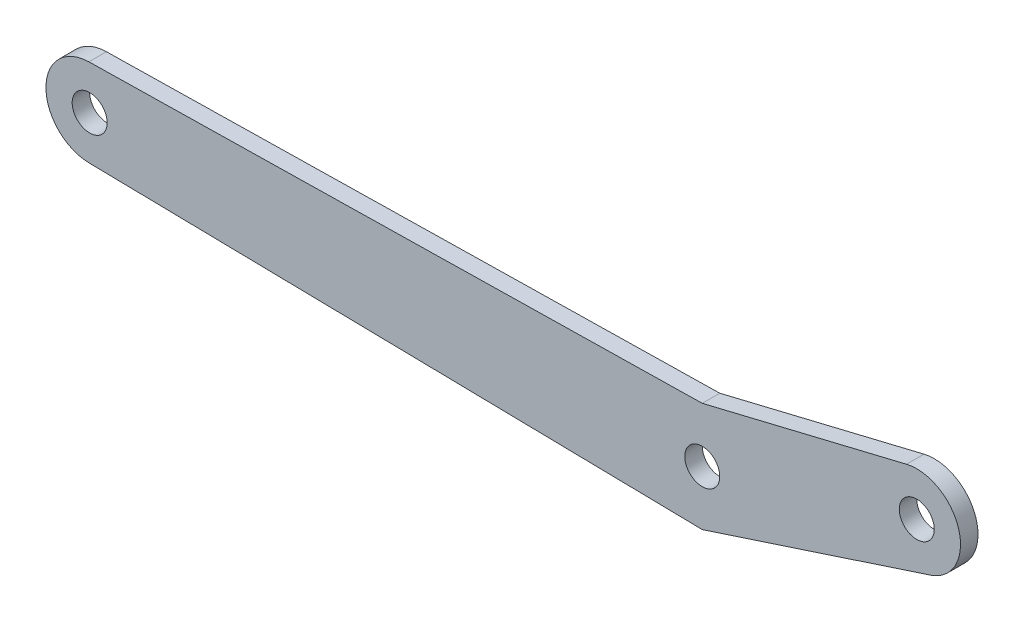
SolidWorks part; units mm, degrees
ref_plane "Alzado" through (0, 0, 0) normal (0, 0, 1) x (1, 0, 0)
ref_plane "Planta" through (0, 0, 0) normal (0, 1, 0) x (1, 0, 0)
ref_plane "Vista lateral" through (0, 0, 0) normal (1, 0, 0) x (0, 0, -1)
sketch "Croquis1" plane through (0, 0, 0) normal (0, 0, 1) x (1, 0, 0)
  line L0 (-140, 0) -> (0, 0) construction
  line L1 (0, 0) -> (49.0243, 14.0575) construction
  line L2 (-140.1784, 9.9984) -> (0, 12.5)
  line L3 (-140.1784, -9.9984) -> (0, -12.5)
  line L4 (0, 12.5) -> (46.6757, 23.7778)
  line L5 (0, -12.5) -> (52.1333, 4.5531)
  line L6 (0, 12.5) -> (0, -12.5) construction
  arc A0 (-140.1784, 9.9984) -> (-140.1784, -9.9984) centre (-140, 0) ccw
  circle A1 centre (0, 0) radius 4
  arc A2 (52.1333, 4.5531) -> (46.6757, 23.7778) centre (49.0243, 14.0575) ccw
  circle A3 centre (49.0243, 14.0575) radius 4
  circle A4 centre (-140, 0) radius 4
  point P13 (-9.8467, 13.3531)
  point P14 (0, 0)
  point P15 (0, 12.5)
  point P17 (44.666, 24.6161)
  dimension "D4" = 8
  dimension "D5" = 20
  dimension "D6" = 8
  dimension "D7" = 20
  dimension "D8" = 8
  dimension "D1" = 16
  dimension "D2" = 51
  dimension "D3" = 140
  dimension "D9" = 25
extrude "Saliente-Extruir1" add sketch "Croquis1" along normal blind 4
